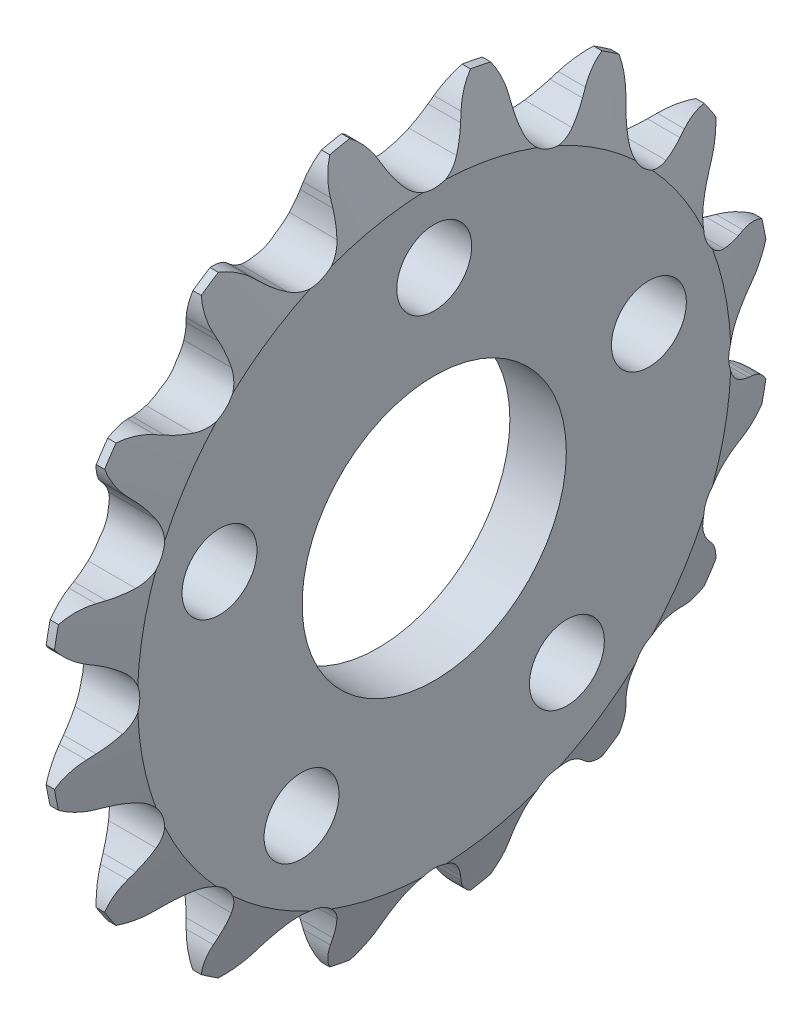
SolidWorks part; units mm, degrees
material "Alloy Steel"
ref_plane "Front Plane" through (0, 0, 0) normal (0, 0, 1) x (1, 0, 0)
ref_plane "Top Plane" through (0, 0, 0) normal (0, 1, 0) x (1, 0, 0)
ref_plane "Right Plane" through (0, 0, 0) normal (1, 0, 0) x (0, 0, -1)
ref_axis "X AXIS" through (-88.99, 0, 0) along (1, 0, 0)
ref_axis "Y AXIS" through (0, -55, 0) along (0, 1, 0)
ref_axis "Z AXIS" through (0, 0, 55) along (0, 0, -1)
other "Freeze***"
sketch "Sketch1" plane through (0, 0, 0) normal (1, 0, 0) x (0, 0, -1)
  line L0 (0, 16.2745) -> (-6.228, 15.0357) construction
  line L1 (-1.896, 16.1459) -> (-2.0514, 16.491)
  line L2 (-1.896, 16.1459) -> (2.0601, 17.928) construction
  line L3 (2.0601, 17.928) -> (0, 16.2745) construction
  line L4 (0, 16.2745) -> (-1.9539, 16.2745) construction
  line L5 (-3.5639, 17.9168) -> (-3.114, 15.6551) construction
  line L6 (0, 16.2745) -> (0, 14.5772) construction
  circle A0 centre (0, 0) radius 16.2745 construction
  arc A1 (-1.3237, 15.2121) -> (0, 14.5772) centre (0, 16.2745) ccw
  arc A2 (-1.3237, 15.2121) -> (-1.896, 16.1459) centre (2.0601, 17.928) cw
  arc A3 (-2.0514, 16.491) -> (-3.5639, 17.9168) centre (-4.534, 15.3726) ccw
sketch "Sketch2" plane through (0, 0, 0) normal (0, 0, 1) x (1, 0, 0)
  line L0 (0, 0) -> (0, 17.862) construction
  line L1 (-0.2064, 17.862) -> (0.2064, 17.862)
  line L2 (0.2064, 17.862) -> (1.397, 14.687)
  line L3 (1.397, 14.687) -> (1.397, 0)
  line L4 (-1.397, 0) -> (1.397, 0)
  line L5 (-1.397, 14.687) -> (-1.397, 0)
  line L6 (-0.2064, 17.862) -> (-1.397, 14.687)
  dimension "D1" = 17.862
  dimension "D2" = 2.794
revolve "Revolve1" add sketch "Sketch2" angle 360 about L4
sketch "Sketch3" plane through (0, 0, 0) normal (1, 0, 0) x (0, 0, -1)
  line L0 (-1.896, 16.1459) -> (-2.0514, 16.491) construction
  line L1 (-1.896, 16.1459) -> (-2.0514, 16.491)
  line L2 (0, 14.5772) -> (0, 0) construction
  line L3 (1.896, 16.1459) -> (2.0514, 16.491)
  arc A0 (-2.0514, 16.491) -> (-3.5639, 17.9168) centre (-4.534, 15.3726) ccw construction
  arc A1 (-1.896, 16.1459) -> (-1.3237, 15.2121) centre (2.0601, 17.928) ccw construction
  arc A2 (-1.3237, 15.2121) -> (0, 14.5772) centre (0, 16.2745) ccw construction
  arc A3 (-2.0514, 16.491) -> (-3.5639, 17.9168) centre (-4.534, 15.3726) ccw
  arc A4 (-1.896, 16.1459) -> (-1.3237, 15.2121) centre (2.0601, 17.928) ccw
  arc A5 (-1.3237, 15.2121) -> (1.3237, 15.2121) centre (0, 16.2745) ccw
  arc A6 (1.896, 16.1459) -> (1.3237, 15.2121) centre (-2.0601, 17.928) cw
  arc A7 (2.0514, 16.491) -> (3.5639, 17.9168) centre (4.534, 15.3726) cw
  arc A8 (-3.5639, 17.9168) -> (3.5639, 17.9168) centre (0, 0) cw
extrude "Cut-Extrude1" cut sketch "Sketch3" against normal through all both and the other way through all contours A8 A3 L1 A4 A5 A6 L3 A7 region at (0, 16.7606, 0)
pattern_circular "CirPattern1" count 16 over 360 about axis through (-88.99, 0, 0) along (1, 0, 0) of "Cut-Extrude1"
sketch "Sketch4" plane through (1.397, 0, 0) normal (1, 0, 0) x (0, 0, -1)
  line L0 (0, 0) -> (0, 11.176) construction
  circle A0 centre (0, 0) radius 6.5405
  circle A1 centre (0, 11.176) radius 1.8542
  circle A2 centre (10.629, 3.4536) radius 1.8542
  circle A3 centre (6.5691, -9.0416) radius 1.8542
  circle A4 centre (-6.5691, -9.0416) radius 1.8542
  circle A5 centre (-10.629, 3.4536) radius 1.8542
  point P15 (0, 0)
  dimension "D1" = 13.081
  dimension "D2" = 5
  dimension "D3" = 3.7084
  dimension "D4" = 11.176
extrude "Cut-Extrude2" cut sketch "Sketch4" against normal through all
equation "\"p\"= 2 / 8"
equation "\"n\"= 16"
equation "\"Dr\"= 0.13"
equation "\"Ds\"= 1.005 * \"Dr\" + 0.003"
equation "\"PD\"= \"p\" * cosec ( 180 / \"n\" )"
equation "\"A\"= 35 + 60 / \"n\""
equation "\"B\"= 18 - 56 / \"n\""
equation "\"ac\"= 0.8 * \"Dr\""
equation "\"ab\"= 1.4 * \"Dr\""
equation "\"D1@Sketch1\"=\"PD\""
equation "\"D2@Sketch1\"=\"p\""
equation "\"D3@Sketch1\"=\"Ds\""
equation "\"D4@Sketch1\"=\"A\""
equation "\"D5@Sketch1\"=\"B\""
equation "\"D6@Sketch1\"=\"ac\""
equation "\"D7@Sketch1\"=\"ab\""
equation "\"D1@Sketch2\"=(\"PD\"+\"p\"/2)/2"
equation "\"D4@Sketch2\"=\"p\"/2"
equation "\"D1@CirPattern1\"=\"n\""
